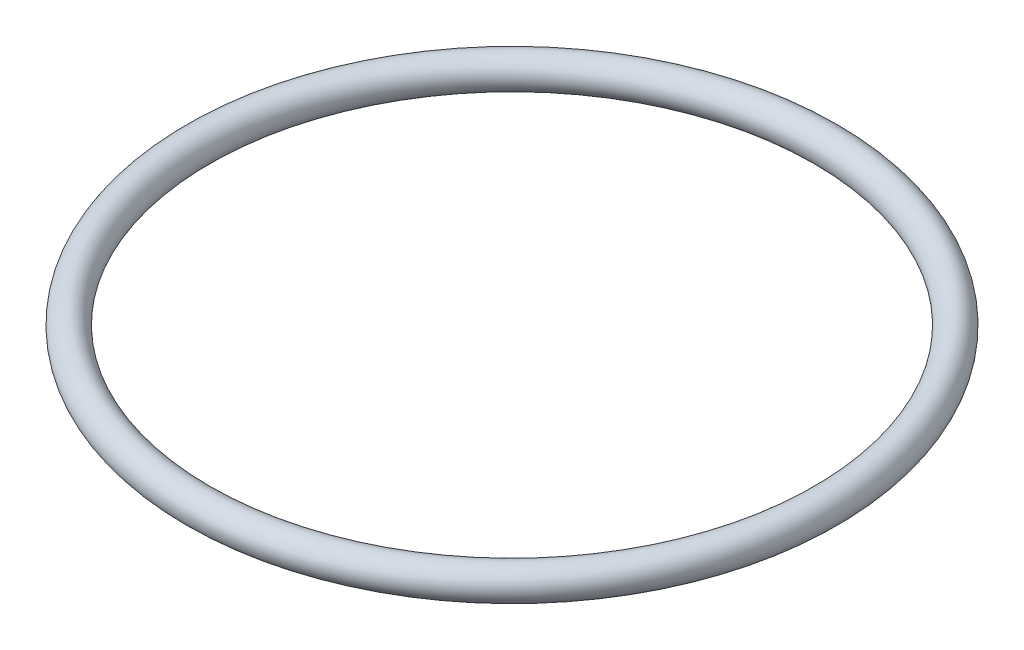
SolidWorks part; units mm, degrees
ref_plane "Front Plane" through (0, 0, 0) normal (0, 0, 1) x (1, 0, 0)
ref_plane "Top Plane" through (0, 0, 0) normal (0, 1, 0) x (1, 0, 0)
ref_plane "Right Plane" through (0, 0, 0) normal (1, 0, 0) x (0, 0, -1)
sketch "Sketch1" plane through (0, 0, 0) normal (0, 0, 1) x (1, 0, 0)
  line L0 (0, 0) -> (0, 64.3129) construction
  circle A0 centre (29.25, 0) radius 1.5
  dimension "D1" = 3
  dimension "D2" = 58.5
revolve "Revolve1" add sketch "Sketch1" angle 360 about L0
